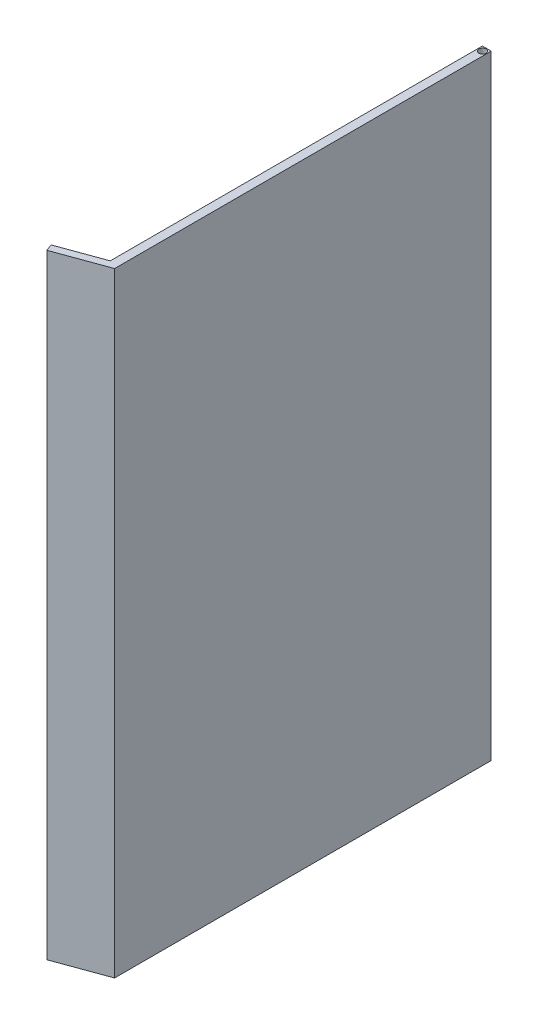
SolidWorks part; units mm, degrees
ref_plane "Front Plane" through (0, 0, 0) normal (0, 0, 1) x (1, 0, 0)
ref_plane "Top Plane" through (0, 0, 0) normal (0, 1, 0) x (1, 0, 0)
ref_plane "Right Plane" through (0, 0, 0) normal (1, 0, 0) x (0, 0, -1)
sketch "Sketch5" plane through (0, 0, 0) normal (0, 1, 0) x (1, 0, 0)
  line L0 (0, 16.7659) -> (0, -34.7141)
  line L1 (0, -34.7141) -> (-6, -36.8979)
  line L2 (-6, -36.8979) -> (-5.658, -37.8376)
  line L3 (-5.658, -37.8376) -> (1.2193, -35.3345)
  line L4 (1.2193, -35.3345) -> (1.2193, 16.7659)
  line L5 (1.2193, 16.7659) -> (0, 16.7659)
  dimension "D1" = 51.48
  dimension "D2" = 6
  dimension "D3" = 110
  dimension "D4" = 1
extrude "Boss-Extrude1" add sketch "Sketch5" along normal blind 85
sketch "Sketch6" plane through (0, 85, 0) normal (0, 1, 0) x (1, 0, 0)
  circle A0 centre (0.617, 16.1615) radius 0.5015
  point P2 (0.7128, 32.2002)
  point P3 (0.6097, 14.0354)
  point P4 (0.617, 16.1615)
extrude "Cut-Extrude1" cut sketch "Sketch6" against normal through all
sketch "Sketch7" plane through (11.1569, 0, 30.6533) normal (-0.342, 0, -0.9397) x (-0.9397, 0, 0.342)
  circle A0 centre (16.9761, 83.7904) radius 0.3002
extrude "Boss-Extrude2" add sketch "Sketch7" along normal blind 0.5
ref_axis "Axis1" through (-5.0324, 83.7904, 35.8083) along (0.342, 0, 0.9397)
sketch "Sketch9" plane through (10.9859, 0, 30.1835) normal (-0.342, 0, -0.9397) x (-0.9397, 0, 0.342)
  point P0 (16.9805, 83.9436)
ref_plane "Plane2" through (-13.6796, -0.4181, 4.979) normal (-0.9393, -0.0287, 0.3419) x (0.3417, 0.0104, 0.9397)
sketch "Sketch10" plane through (-13.6796, -0.4181, 4.979) normal (-0.9393, -0.0287, 0.3419) x (0.3417, 0.0104, 0.9397)
  line L0 (33.0022, 84.2032) -> (33.0022, 83.903)
  line L1 (32.8061, 83.905) -> (33.692, 83.8958) construction
  line L2 (33.0022, 83.903) -> (32.436, 83.9089)
  line L3 (32.436, 83.9089) -> (33.0022, 84.2032)
  point P5 (32.436, 83.9089)
revolve "Revolve1" add sketch "Sketch10" angle 360 about L2
pattern_linear "LPattern1" count 9 spacing 10 along (0, -1, 0) of "Revolve1", "Boss-Extrude2"
